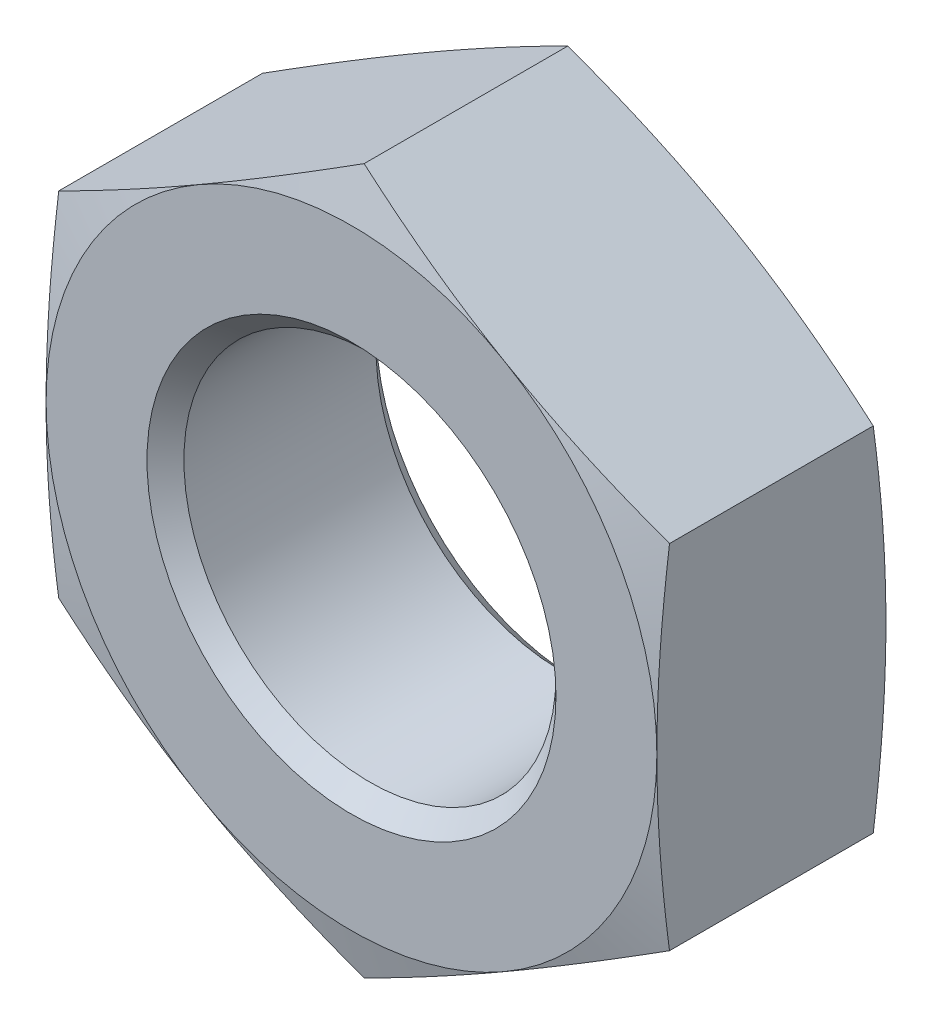
SolidWorks part; units mm, degrees
ref_plane "Front Plane" through (0, 0, 0) normal (0, 0, 1) x (1, 0, 0)
ref_plane "Top Plane" through (0, 0, 0) normal (0, 1, 0) x (1, 0, 0)
ref_plane "Right Plane" through (0, 0, 0) normal (1, 0, 0) x (0, 0, -1)
sketch "Sketch1" plane through (0, 0, 0) normal (1, 0, 0) x (0, 0, -1)
  line L0 (0, 0) -> (0, 14.224)
  line L1 (0, 14.224) -> (0.7623, 17.0688)
  line L2 (0.7623, 17.0688) -> (9.9057, 17.0688)
  line L3 (9.9057, 17.0688) -> (10.668, 14.224)
  line L4 (10.668, 14.224) -> (10.668, 0)
  line L5 (10.668, 0) -> (0, 0)
  line L6 (10.668, 0) -> (0, 0) construction
sketch "Sketch2" plane through (0, 0, 0) normal (0, 0, 1) x (1, 0, 0)
  line L0 (-28.448, 28.448) -> (-28.448, -28.448)
  line L1 (-28.448, -28.448) -> (28.448, -28.448)
  line L2 (28.448, -28.448) -> (28.448, 28.448)
  line L3 (28.448, 28.448) -> (-28.448, 28.448)
  line L4 (-14.224, 8.2122) -> (-14.224, -8.2122)
  line L5 (-14.224, -8.2122) -> (0, -16.4245)
  line L6 (0, -16.4245) -> (14.224, -8.2122)
  line L7 (14.224, -8.2122) -> (14.224, 8.2122)
  line L8 (14.224, 8.2122) -> (0, 16.4245)
  line L9 (0, 16.4245) -> (-14.224, 8.2122)
revolve "Revolve1" add sketch "Sketch1" angle 360 about L6 reverse direction yes
extrude "Cut-Extrude1" cut sketch "Sketch2" against normal blind 10.668
sketch "Sketch3" plane through (0, 0, 0) normal (1, 0, 0) x (0, 0, -1)
  line L0 (0, 0) -> (0, 9.525)
  line L1 (0, 9.525) -> (0.8598, 8.6652)
  line L2 (0.8598, 8.6652) -> (9.8082, 8.6652)
  line L3 (9.8082, 8.6652) -> (10.668, 9.525)
  line L4 (10.668, 9.525) -> (10.668, 0)
  line L5 (10.668, 0) -> (0, 0)
  line L6 (10.668, 0) -> (0, 0) construction
revolve "Cut-Revolve1" cut sketch "Sketch3" angle 360 about L6 reverse direction yes
cosmetic thread "Cosmetic Thread1" parameters "D1"=10.668, "D2"=19.05
ref_plane "NUT XY" through (0, 0, 0) normal (0, 0, 1) x (1, 0, 0)
ref_plane "NUT XZ" through (0, 0, 0) normal (0, -1, 0) x (-1, 0, 0)
ref_plane "NUT YZ" through (0, 0, 0) normal (1, 0, 0) x (0, 0, -1)
ref_axis "NUT X" through (-80.9, 0, 0) along (1, 0, 0)
ref_axis "NUT Y" through (0, -50, 0) along (0, 1, 0)
ref_axis "NUT Z" through (0, 0, 80.9) along (0, 0, -1)
sketch3d "NUT"
  point P0 (0, 0, 0)
ref_plane "a1 XY" through (0, 0, 0) normal (0, 0, 1) x (1, 0, 0)
ref_plane "a1 XZ" through (0, 14.224, 0) normal (0, -1, 0) x (-1, 0, 0)
ref_plane "a1 YZ" through (-14.224, 0, 0) normal (1, 0, 0) x (0, 0, -1)
ref_axis "a1 X" through (-80.9, 14.224, 0) along (1, 0, 0)
ref_axis "a1 Y" through (-14.224, -50, 0) along (0, 1, 0)
ref_axis "a1 Z" through (-14.224, 14.224, 80.9) along (0, 0, -1)
sketch3d "a1"
  point P0 (-14.224, 14.224, 0)
ref_plane "a2 XY" through (0, 0, 0) normal (0, 0, 1) x (1, 0, 0)
ref_plane "a2 XZ" through (0, 14.224, 0) normal (0, -1, 0) x (-1, 0, 0)
ref_plane "a2 YZ" through (14.224, 0, 0) normal (1, 0, 0) x (0, 0, -1)
ref_axis "a2 X" through (-80.9, 14.224, 0) along (1, 0, 0)
ref_axis "a2 Y" through (14.224, -50, 0) along (0, 1, 0)
ref_axis "a2 Z" through (14.224, 14.224, 80.9) along (0, 0, -1)
sketch3d "a2"
  point P0 (14.224, 14.224, 0)
ref_plane "b1 XY" through (0, 0, 0) normal (1, 0, 0) x (0, 0, -1)
ref_plane "b1 XZ" through (0, 14.224, 0) normal (0, -1, 0) x (-1, 0, 0)
ref_plane "b1 YZ" through (0, 0, 0) normal (0, 0, -1) x (-1, 0, 0)
ref_axis "b1 X" through (0, 14.224, 80.9) along (0, 0, -1)
ref_axis "b1 Y" through (0, -50, 0) along (0, 1, 0)
ref_axis "b1 Z" through (80.9, 14.224, 0) along (-1, 0, 0)
sketch3d "b1"
  point P0 (0, 14.224, 0)
ref_plane "b2 XY" through (0, 0, 0) normal (1, 0, 0) x (0, 0, -1)
ref_plane "b2 XZ" through (0, 14.224, 0) normal (0, -1, 0) x (-1, 0, 0)
ref_plane "b2 YZ" through (0, 0, -10.668) normal (0, 0, -1) x (-1, 0, 0)
ref_axis "b2 X" through (0, 14.224, 80.9) along (0, 0, -1)
ref_axis "b2 Y" through (0, -50, -10.668) along (0, 1, 0)
ref_axis "b2 Z" through (80.9, 14.224, -10.668) along (-1, 0, 0)
sketch3d "b2"
  point P0 (0, 14.224, -10.668)
ref_plane "e XY" through (0, 0, 0) normal (1, 0, 0) x (0, 0, -1)
ref_plane "e XZ" through (0, 0, 0) normal (0, -1, 0) x (-1, 0, 0)
ref_plane "e YZ" through (0, 0, -10.668) normal (0, 0, -1) x (-1, 0, 0)
ref_axis "e X" through (0, 0, 80.9) along (0, 0, -1)
ref_axis "e Y" through (0, -50, -10.668) along (0, 1, 0)
ref_axis "e Z" through (80.9, 0, -10.668) along (-1, 0, 0)
sketch3d "e"
  point P0 (0, 0, -10.668)
ref_plane "ol1 XY" through (0, 0, 0) normal (0, 1, 0) x (1, 0, 0)
ref_plane "ol1 XZ" through (0, 0, -14.224) normal (0, 0, 1) x (1, 0, 0)
ref_plane "ol1 YZ" through (0, 0, 0) normal (1, 0, 0) x (0, 0, -1)
ref_axis "ol1 X" through (-80.9, 0, -14.224) along (1, 0, 0)
ref_axis "ol1 Y" through (0, 0, 50) along (0, 0, -1)
ref_axis "ol1 Z" through (0, 50, -14.224) along (0, -1, 0)
sketch3d "ol1"
  point P0 (0, 0, -14.224)
ref_plane "ol2 XY" through (0, 0, 0) normal (0, 1, 0) x (1, 0, 0)
ref_plane "ol2 XZ" through (0, 0, -14.224) normal (0, 0, 1) x (1, 0, 0)
ref_plane "ol2 YZ" through (10.668, 0, 0) normal (1, 0, 0) x (0, 0, -1)
ref_axis "ol2 X" through (-80.9, 0, -14.224) along (1, 0, 0)
ref_axis "ol2 Y" through (10.668, 0, 50) along (0, 0, -1)
ref_axis "ol2 Z" through (10.668, 50, -14.224) along (0, -1, 0)
sketch3d "ol2"
  point P0 (10.668, 0, -14.224)
ref_plane "th1 XY" through (0, 0, 0) normal (1, 0, 0) x (0, 0, -1)
ref_plane "th1 XZ" through (0, 9.525, 0) normal (0, -1, 0) x (-1, 0, 0)
ref_plane "th1 YZ" through (0, 0, -10.668) normal (0, 0, -1) x (-1, 0, 0)
ref_axis "th1 X" through (0, 9.525, 80.9) along (0, 0, -1)
ref_axis "th1 Y" through (0, -50, -10.668) along (0, 1, 0)
ref_axis "th1 Z" through (80.9, 9.525, -10.668) along (-1, 0, 0)
sketch3d "th1"
  point P0 (0, 9.525, -10.668)
ref_plane "th2 XY" through (0, 0, 0) normal (1, 0, 0) x (0, 0, -1)
ref_plane "th2 XZ" through (0, -9.525, 0) normal (0, -1, 0) x (-1, 0, 0)
ref_plane "th2 YZ" through (0, 0, -10.668) normal (0, 0, -1) x (-1, 0, 0)
ref_axis "th2 X" through (0, -9.525, 80.9) along (0, 0, -1)
ref_axis "th2 Y" through (0, -50, -10.668) along (0, 1, 0)
ref_axis "th2 Z" through (80.9, -9.525, -10.668) along (-1, 0, 0)
sketch3d "th2"
  point P0 (0, -9.525, -10.668)
